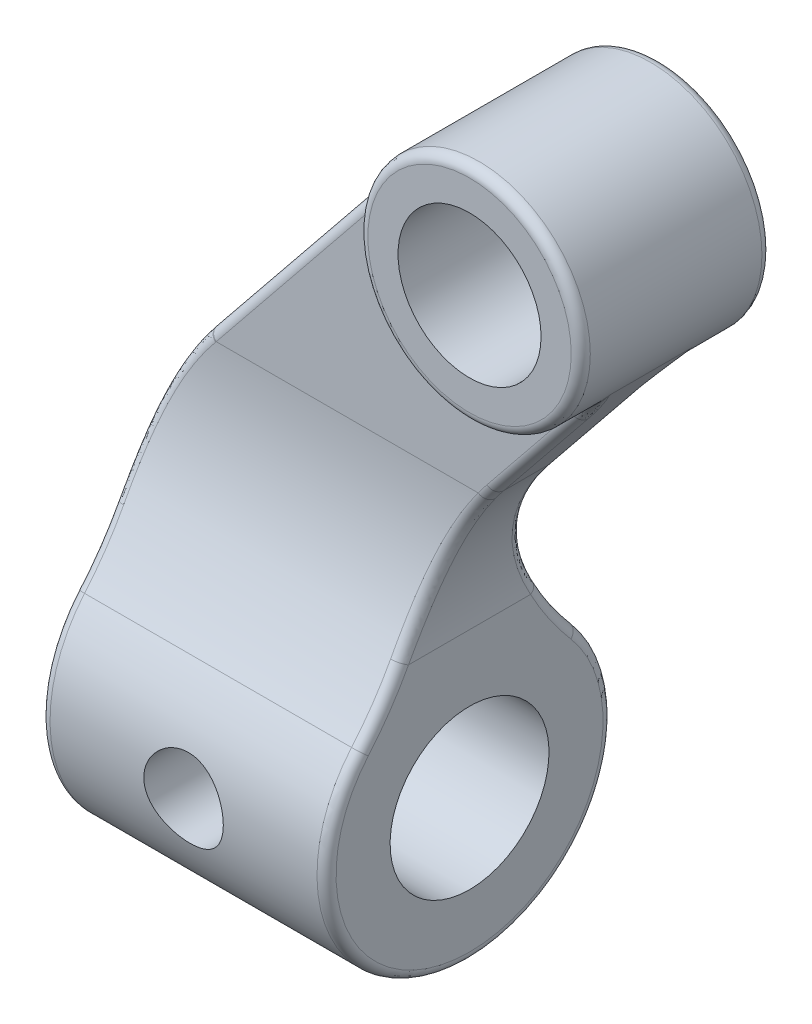
SolidWorks part; units mm, degrees
material "AISI 1020"
ref_plane "Front Plane" through (0, 0, 0) normal (0, 0, 1) x (1, 0, 0)
ref_plane "Top Plane" through (0, 0, 0) normal (0, 1, 0) x (1, 0, 0)
ref_plane "Right Plane" through (0, 0, 0) normal (1, 0, 0) x (0, 0, -1)
sketch "Sketch1" plane through (0, 0, 0) normal (0, 0, 1) x (1, 0, 0)
  line L0 (-90, 0) -> (-15, 92.8078)
  line L1 (0, 0) -> (39.4444, 48.81)
  line L2 (-17.7778, -96.141) -> (-107.7778, -96.141)
  line L3 (-107.7778, -50.2831) -> (-107.7778, -141.9989)
  line L4 (-107.7778, -141.9989) -> (-17.7778, -141.9989)
  line L5 (-17.7778, -141.9989) -> (-17.7778, -50.2831)
  line L6 (-17.7778, -50.2831) -> (-17.7778, 9.3787) construction
  line L7 (0, 0) -> (-48.2745, -59.7367) construction
  line L8 (-90, 0) -> (-130.5394, -50.165) construction
  line L9 (-107.7778, -50.2831) -> (-107.7778, 14.6425) construction
  line L10 (-107.7778, -21.9989) -> (-17.7778, -21.9989) construction
  circle A0 centre (12.2222, 70.8089) radius 35
  circle A1 centre (12.2222, 70.8089) radius 22.5
  arc A3 (0, 0) -> (-17.7778, -50.2831) centre (62.2222, -50.2831) ccw
  arc A4 (-90, 0) -> (-107.7778, -50.2831) centre (-27.7778, -50.2831) ccw
  dimension "D1" = 45
  dimension "D2" = 70
  dimension "D3" = 80
  dimension "D4" = 80
  dimension "D5" = 120
  dimension "D6" = 90
  dimension "D7" = 30
extrude "Boss-Extrude1" add sketch "Sketch1" along normal mid plane 20 contours L0 A4 A3 L1 A0 region at (-49.7299, -22.6753, 0)
extrude "Boss-Extrude2" add sketch "Sketch1<3>" along normal mid plane 60 contours A0 A1 region at (23.5589, 102.8739, 0)
sketch "Sketch1<3>" plane through (0, 0, 0) normal (0, 0, 1) x (1, 0, 0) same geometry as "Sketch1"
ref_plane "Plane2" through (-107.7778, 0, 0) normal (-1, 0, 0) x (0, 0, 1)
sketch "Sketch3" plane through (-107.7778, 0, 0) normal (-1, 0, 0) x (0, 0, 1)
  line L1 (10, -96.141) -> (-10, -96.141) construction
  circle A0 centre (0, -96.141) radius 45
  circle A1 centre (0, -96.141) radius 25
  point P7 (0, -96.141)
  dimension "D1" = 90
  dimension "D2" = 20
extrude "Boss-Extrude4" add sketch "Sketch3" against normal blind 90
extrude "Cut-Extrude1" cut sketch "Sketch3<2>" against normal through all contours A1
sketch "Sketch3<2>" plane through (-107.7778, 0, 0) normal (-1, 0, 0) x (0, 0, 1) same geometry as "Sketch3"
fillet "Fillet2" radius 3 3 edges at (47.2222, 70.8089, -30) (-9.7767, 43.5867, -10) (-9.7767, 43.5867, 10)
fillet "Fillet3" radius 100 1 edges at (-62.7778, -52.2662, 10)
fillet "Fillet4" radius 100 1 edges at (-62.7778, -52.2662, -10)
fillet "Fillet5" radius 3 23 edges at (-105.1075, -29.7865, 14.0344) (-102.2605, -21.0886, -11.9038) (-57.1508, 40.6489, 10) (-90.6617, -0.83, 10) (-107.7778, -58.8438, 27.9572) (-107.7778, -141.141, 0) (-107.7778, -58.8438, -27.9572) (-57.1508, 40.6489, -10) (-90.6617, -0.83, -10) (33.9141, 41.9666, 10.6874) (-12.2605, -21.0886, 11.9038) (-15.1075, -29.7865, -14.0344) (33.9141, 41.9666, -10.6874) (-20.5303, 85.9644, -10.6874) (-20.5303, 85.9644, 10.6874) (47.2222, 70.8089, 30) (15.0715, 18.65, 10) (-0.6617, -0.83, 10) (-17.7778, -58.8438, 27.9572) (-17.7778, -141.141, 0) (-17.7778, -58.8438, -27.9572) (-0.6617, -0.83, -10) (15.0715, 18.65, -10)
sketch "Sketch5" plane through (0, 0, 0) normal (0, 0, 1) x (1, 0, 0)
  line L1 (-107.7778, -141.9989) -> (-17.7778, -141.9989) construction
  line L2 (-62.7778, -50.7166) -> (-62.7778, -141.9989) construction
  circle A0 centre (-62.7778, -96.9989) radius 12.5
  dimension "D1" = 25
  dimension "D2" = 45
extrude "Cut-Extrude2" cut sketch "Sketch5" against normal through all both and the other way through all
